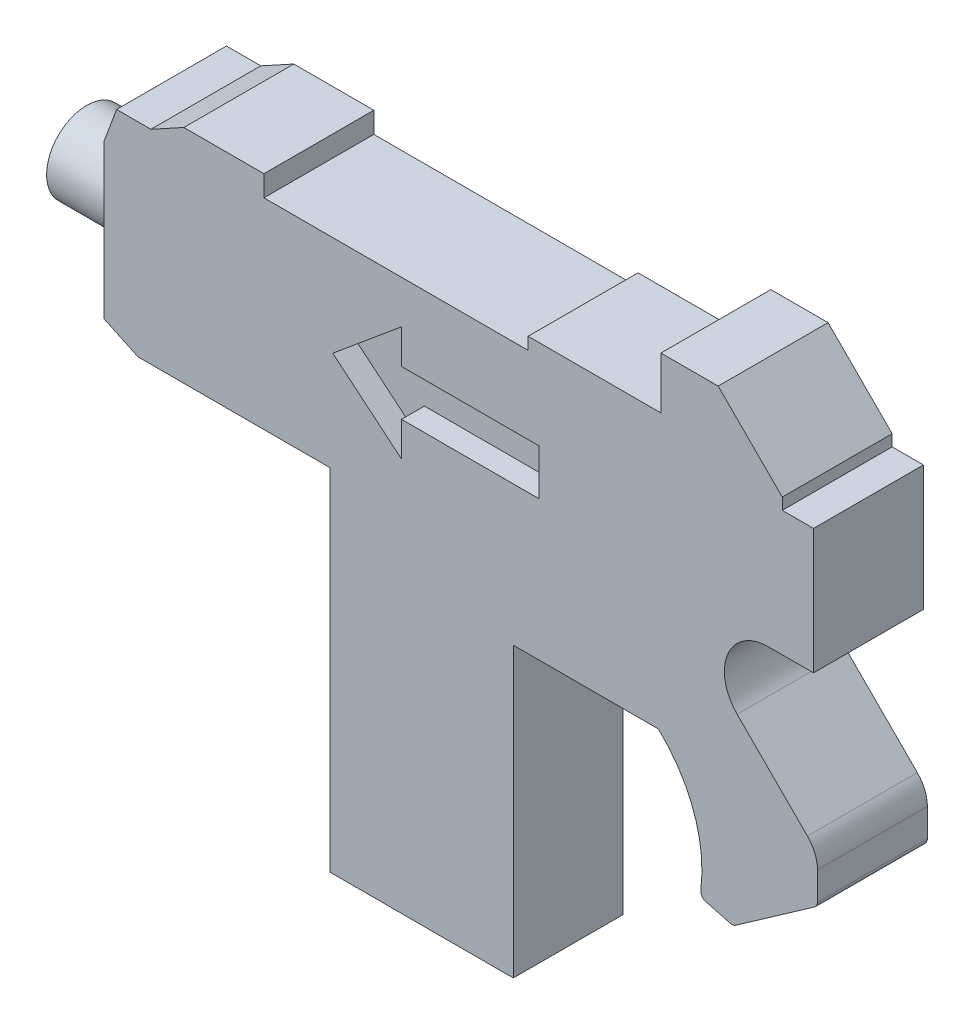
SolidWorks part; units mm, degrees
ref_plane "Front Plane" through (0, 0, 0) normal (0, 0, 1) x (1, 0, 0)
ref_plane "Top Plane" through (0, 0, 0) normal (0, 1, 0) x (1, 0, 0)
ref_plane "Right Plane" through (0, 0, 0) normal (1, 0, 0) x (0, 0, -1)
sketch "Sketch1" plane through (0, 0, 0) normal (0, 0, 1) x (1, 0, 0)
  line L0 (-141.3513, -198.1) -> (-141.3513, -131.187)
  line L1 (-141.3513, -198.1) -> (-141.3513, -186.3462) construction
  line L2 (-141.3513, -198.1) -> (-126.3513, -205.1) construction
  line L3 (-141.3513, -131.187) -> (-135.7835, -116.187)
  line L4 (-135.7835, -116.187) -> (-120.7835, -116.187)
  line L5 (-120.7835, -116.187) -> (-106.3843, -108.305)
  line L6 (-106.3843, -108.305) -> (-71.4264, -108.305)
  line L7 (-71.4264, -108.305) -> (-71.4264, -117.4431)
  line L8 (-29.3513, -117.4431) -> (-92.1837, -117.4431) construction
  line L9 (-71.4264, -117.4431) -> (43.9919, -117.4431)
  line L10 (43.9919, -117.4431) -> (43.9919, -112.1) construction
  line L11 (43.9919, -117.4431) -> (43.9919, -112.1)
  line L12 (43.9919, -112.1) -> (101.9919, -112.1)
  line L13 (101.9919, -117.4431) -> (101.9919, -91.4431) construction
  line L14 (43.9919, -112.1) -> (138.9919, -112.1) construction
  line L15 (101.9919, -112.1) -> (101.9919, -89.4431)
  line L16 (101.9919, -89.4431) -> (126.9919, -89.4431)
  line L17 (126.9919, -89.4431) -> (154.9919, -117.4431)
  line L18 (154.9919, -117.4431) -> (154.9919, -122.4431)
  line L19 (154.9919, -122.4431) -> (168.6487, -122.4431)
  line L20 (168.6487, -122.4431) -> (168.6487, -177.1)
  line L21 (168.6487, -177.1) -> (148.6487, -177.1)
  line L22 (169.0927, -265.4487) -> (165.5191, -267.9509) construction
  line L23 (170.3719, -250.7661) -> (170.3719, -262.9912) construction
  line L24 (135.2548, -209.4358) -> (165.9785, -240.1595) construction
  line L25 (169.0927, -265.4487) -> (134.656, -289.5615)
  line L26 (170.3719, -250.7661) -> (170.3719, -262.9912)
  line L27 (135.2548, -209.4358) -> (165.9785, -240.1595)
  line L28 (132.1588, -290.0018) -> (121.6122, -287.1758) construction
  line L29 (132.1588, -290.0018) -> (121.6122, -287.1758)
  line L30 (37.5, -238.1) -> (37.5, -358.1) construction
  line L32 (37.5, -238.1) -> (37.5, -358.1)
  line L33 (100.864, -232.2019) -> (37.5, -232.2019)
  line L34 (37.5, -232.2019) -> (37.5, -238.1)
  line L35 (37.5, -358.1) -> (-42.5, -358.1)
  line L36 (-42.5, -358.1) -> (-42.5, -205.1)
  line L37 (-42.5, -205.1) -> (-126.3513, -205.1)
  line L38 (-126.3513, -205.1) -> (-141.3513, -198.1)
  line L39 (103.9919, -89.4431) -> (126.9919, -89.4431) construction
  line L40 (126.9919, -89.4431) -> (154.9919, -117.4431) construction
  line L41 (168.6487, -172.1197) -> (168.6487, -128.1) construction
  arc A0 (169.0927, -265.4487) -> (170.3719, -262.9912) centre (167.3719, -262.9912) ccw construction
  arc A1 (170.3719, -250.7661) -> (165.9785, -240.1595) centre (155.3719, -250.7661) ccw construction
  arc A2 (137.6571, -180.6153) -> (135.2548, -209.4358) centre (148.6487, -196.0419) ccw construction
  arc A3 (148.6487, -177.1) -> (137.6571, -180.6153) centre (148.6487, -196.0419) ccw construction
  arc A4 (169.0927, -265.4487) -> (170.3719, -262.9912) centre (167.3719, -262.9912) ccw
  arc A5 (170.3719, -250.7661) -> (165.9785, -240.1595) centre (155.3719, -250.7661) ccw
  arc A6 (137.6571, -180.6153) -> (135.2548, -209.4358) centre (148.6487, -196.0419) ccw
  arc A7 (148.6487, -177.1) -> (137.6571, -180.6153) centre (148.6487, -196.0419) ccw
  arc A8 (119.4135, -283.8931) -> (100.864, -232.2019) centre (59.6617, -276.1613) ccw construction
  arc A9 (119.4135, -283.8931) -> (121.6122, -287.1758) centre (122.3887, -284.278) ccw construction
  arc A10 (132.1588, -290.0018) -> (134.656, -289.5615) centre (132.9353, -287.104) ccw construction
  arc A11 (119.4135, -283.8931) -> (100.864, -232.2019) centre (59.6617, -276.1613) ccw
  arc A12 (119.4135, -283.8931) -> (121.6122, -287.1758) centre (122.3887, -284.278) ccw
  arc A13 (132.1588, -290.0018) -> (134.656, -289.5615) centre (132.9353, -287.104) ccw
extrude "Boss-Extrude1" add sketch "Sketch1" along normal up to surface (48 mm away)
sketch "Sketch2" plane through (-141.3513, 0, 0) normal (-1, 0, 0) x (0, 0, 1)
  arc A0 (10.595, -170.3572) -> (42.9932, -161.6761) centre (25.5, -161.187) ccw construction
  circle A1 centre (25.5, -161.187) radius 17.5
extrude "Boss-Extrude2" add sketch "Sketch2" along normal up to surface (30 mm away)
sketch "Sketch4" plane through (0, 0, 48) normal (0, 0, 1) x (1, 0, 0)
  line L0 (-171.3513, -161.187) -> (168.6487, -161.187) construction
  line L1 (-171.3513, -143.687) -> (-171.3513, -178.687) construction
  line L2 (168.6487, -177.1) -> (168.6487, -122.4431) construction
  line L3 (-41.3513, -161.187) -> (-11.3513, -136.187)
  line L4 (-11.3513, -136.187) -> (-11.3513, -151.187)
  line L5 (-11.3513, -151.187) -> (48.6487, -151.187)
  line L6 (48.6487, -151.187) -> (48.6487, -171.187)
  line L7 (48.6487, -171.187) -> (-11.3513, -171.187)
  line L8 (-11.3513, -171.187) -> (-11.3513, -186.187)
  line L9 (-11.3513, -186.187) -> (-41.3513, -161.187)
  line L10 (-11.3513, -151.187) -> (-11.3513, -161.187) construction
  line L11 (-11.3513, -161.187) -> (-11.3513, -171.187) construction
  line L12 (-141.3513, -131.187) -> (-141.3513, -198.1) construction
  dimension "D1" = 100
  dimension "D2" = 120
  dimension "D3" = 30
  dimension "D4" = 50
  dimension "D5" = 20
extrude "Cut-Extrude1" cut sketch "Sketch4" against normal blind 10
